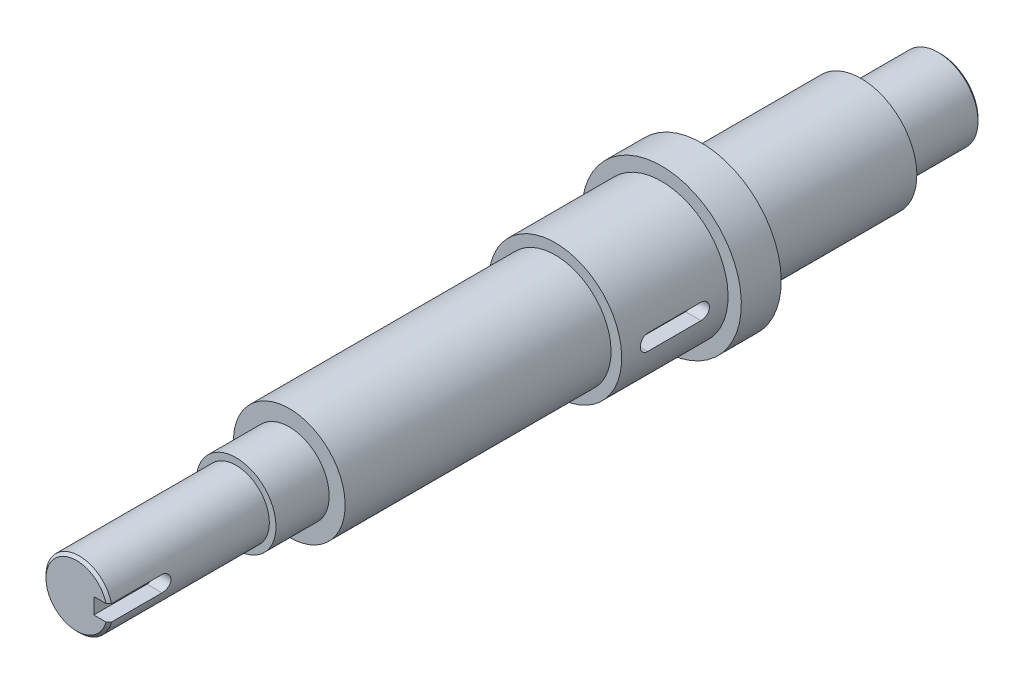
SolidWorks part; units mm, degrees
ref_plane "Front Plane" through (0, 0, 0) normal (0, 0, 1) x (1, 0, 0)
ref_plane "Top Plane" through (0, 0, 0) normal (0, 1, 0) x (1, 0, 0)
ref_plane "Right Plane" through (0, 0, 0) normal (1, 0, 0) x (0, 0, -1)
sketch "Sketch2" plane through (0, 0, 0) normal (1, 0, 0) x (0, 0, -1)
  line L0 (0, 0) -> (-225, 0) construction
  line L1 (-225, 12.5) -> (-225, 0)
  line L2 (-45, 21) -> (-45, 25)
  line L3 (-225, 12.5) -> (-165, 12.5)
  line L4 (-165, 12.5) -> (-165, 15)
  line L5 (-165, 15) -> (-145, 15)
  line L6 (-145, 15) -> (-145, 21)
  line L7 (-145, 21) -> (-45, 21)
  line L8 (-45, 25) -> (-5, 25)
  line L9 (-5, 25) -> (-5, 30)
  line L10 (-5, 30) -> (10, 30)
  line L11 (10, 30) -> (10, 21)
  line L12 (10, 21) -> (70, 21)
  line L13 (70, 21) -> (70, 15)
  line L14 (70, 15) -> (100, 15)
  line L15 (100, 15) -> (100, 0)
  line L16 (100, 0) -> (0, 0) construction
  line L17 (-225, 0) -> (100, 0)
  point P15 (-155, 15)
  point P21 (0, 0)
  dimension "D1" = 25
  dimension "D2" = 30
  dimension "D3" = 42
  dimension "D4" = 325
  dimension "D5" = 50
  dimension "D6" = 60
  dimension "D7" = 100
  dimension "D8" = 15
  dimension "D9" = 30
  dimension "D10" = 60
  dimension "D11" = 40
  dimension "D12" = 60
  dimension "D13" = 100
  dimension "D14" = 20
revolve "Revolve1" add sketch "Sketch2" angle 360 about L17
hole_wizard "M8x1.0 Tapped Hole1" positions "3DSketch1" profile "Sketch3" tap size "M8x1.0" standard "ANSI Metric"
sketch3d "3DSketch1"
  line L0 (0, 0, -100) -> (0, 0, -70) construction
  point P0 (0, 0, -100)
sketch "Sketch3" plane through (0, 0, -100) normal (1, 0, 0) x (0, 1, 0)
  line L0 (0, 0) -> (0, 21.103)
  line L1 (0, 21.103) -> (3.5, 19)
  line L2 (3.5, 19) -> (3.5, 0)
  line L5 (3.5, 0) -> (0, 0)
  line L10 (0, 21.103) -> (-3.5, 19) construction
  line L11 (0, -6.35) -> (0, 107.95) construction
  dimension "Tap Drill Dia." = 7
  dimension "Tap Drill Depth" = 19
  dimension "Drill Angle" = 118
cosmetic thread "Hole Thread1" parameters "D1"=16, "D2"=8
ref_plane "Plane1" through (12.5, 0, 0) normal (1, 0, 0) x (0, 0, -1)
sketch "Sketch4" plane through (12.5, 0, 0) normal (1, 0, 0) x (0, 0, -1)
  line L0 (-225, 0) -> (-205, 0) construction
  line L1 (-225, 12.5) -> (-225, -12.5) construction
  line L2 (-205, 3) -> (-225, 3)
  line L3 (-225, 3) -> (-225, -3)
  line L4 (-205, -3) -> (-225, -3)
  arc A0 (-205, -3) -> (-205, 3) centre (-205, 0) ccw
  dimension "D1" = 6
  dimension "D2" = 20
extrude "Cut-Extrude3" cut sketch "Sketch4" against normal blind 6
ref_plane "Plane2" through (25, 0, 0) normal (1, 0, 0) x (0, 0, -1)
sketch "Sketch5" plane through (25, 0, 0) normal (1, 0, 0) x (0, 0, -1)
  line L0 (-5, 25) -> (-5, -25) construction
  line L1 (-15, 0) -> (-5, 0) construction
  line L2 (-35, 0) -> (-45, 0) construction
  line L3 (-35, 0) -> (-15, 0) construction
  line L4 (-35, 3) -> (-15, 3)
  line L5 (-35, -3) -> (-15, -3)
  line L6 (-45, 21) -> (-45, -21) construction
  arc A0 (-35, 3) -> (-35, -3) centre (-35, 0) ccw
  arc A1 (-15, -3) -> (-15, 3) centre (-15, 0) ccw
  point P4 (-25, 0)
  dimension "D1" = 6
  dimension "D2" = 20
  dimension "D3" = 10
extrude "Cut-Extrude4" cut sketch "Sketch5" against normal blind 6
chamfer "Chamfer1" distance 1 angle 45 2 edges at (-12.5, 0, 225) (0, -15, -100)
